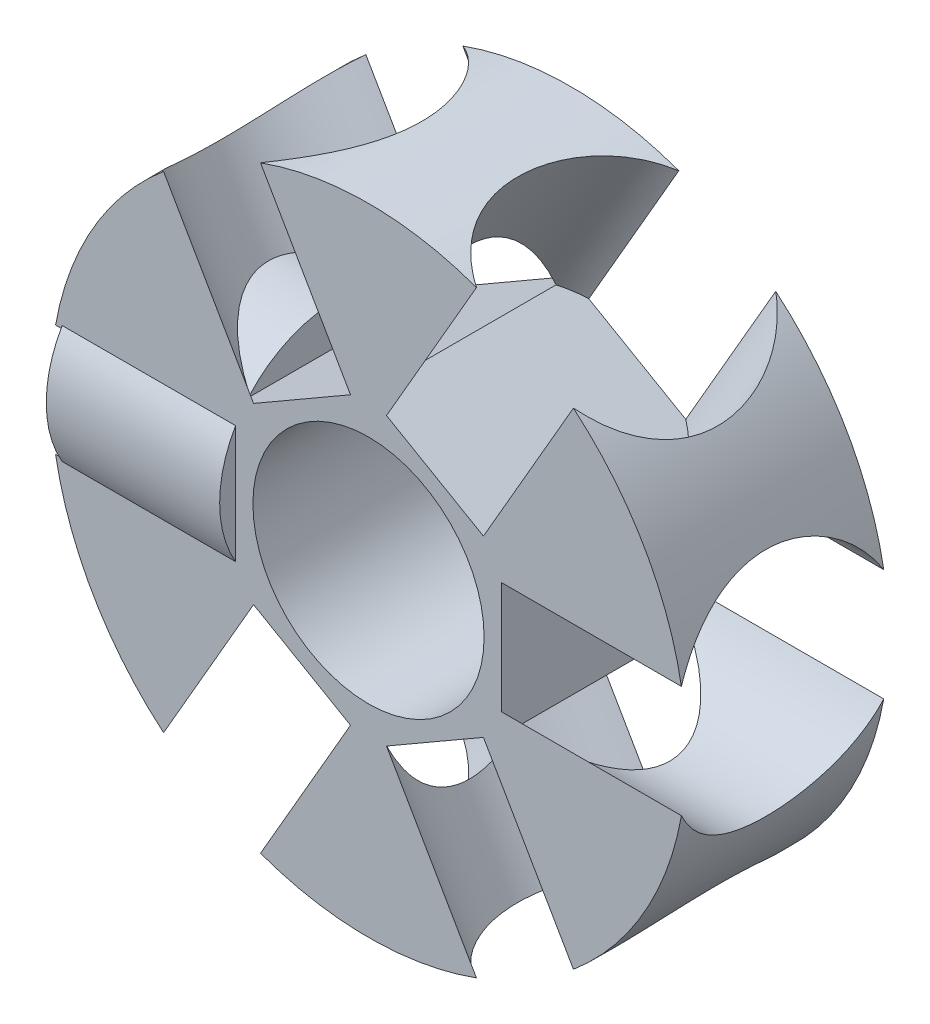
SolidWorks part; units mm, degrees
ref_plane "Top Plane" through (0, 0, 0) normal (0, 0, 1) x (1, 0, 0)
ref_plane "Right Plane" through (0, 0, 0) normal (0, 1, 0) x (1, 0, 0)
ref_plane "Front Plane" through (0, 0, 0) normal (1, 0, 0) x (0, 0, -1)
ref_axis "x-axis" through (-88.99, 0, 0) along (1, 0, 0)
ref_axis "y-axis" through (0, -55, 0) along (0, 1, 0)
ref_axis "z-axis" through (0, 0, 55) along (0, 0, -1)
sketch "Sketch1" plane through (0, 0, 0) normal (0, 0, 1) x (1, 0, 0)
  line L8 (-19.9785, 0) -> (0, 0) construction
  line L16 (0, 0) -> (0, -20.7846) construction
  line L23 (0, 0) -> (0, -20.7846) construction
  circle A0 centre (0, 0) radius 4
  circle A3 centre (0, 0) radius 11
  dimension "D1" = 8
  dimension "D2" = 22
extrude "Boss-Extrude1" add sketch "Sketch1" along normal mid plane 7
ref_plane "Plane1" through (-11, 0, 0) normal (-1, 0, 0) x (0, 0, 1)
sketch "Sketch2" plane through (-11, -17.1931, 0) normal (1, 0, 0) x (0, -1, 0)
  circle A0 centre (-17.1931, 0) radius 4
  dimension "D1" = 8
extrude "Cut-Extrude3" cut sketch "Sketch2" along normal blind 6.4
pattern_circular "CirPattern1" count 6 over 360 about axis through (0, 0, 3.5) along (0, 0, 1) of "Cut-Extrude3"
sketch "Sketch3" plane through (-4.6, 0, 0) normal (-1, 0, 0) x (0, -1, 0)
  circle A0 centre (0, 0) radius 4.05
  dimension "D1" = 4.05
extrude "Boss-Extrude2" add sketch "Sketch3" along normal blind 6
